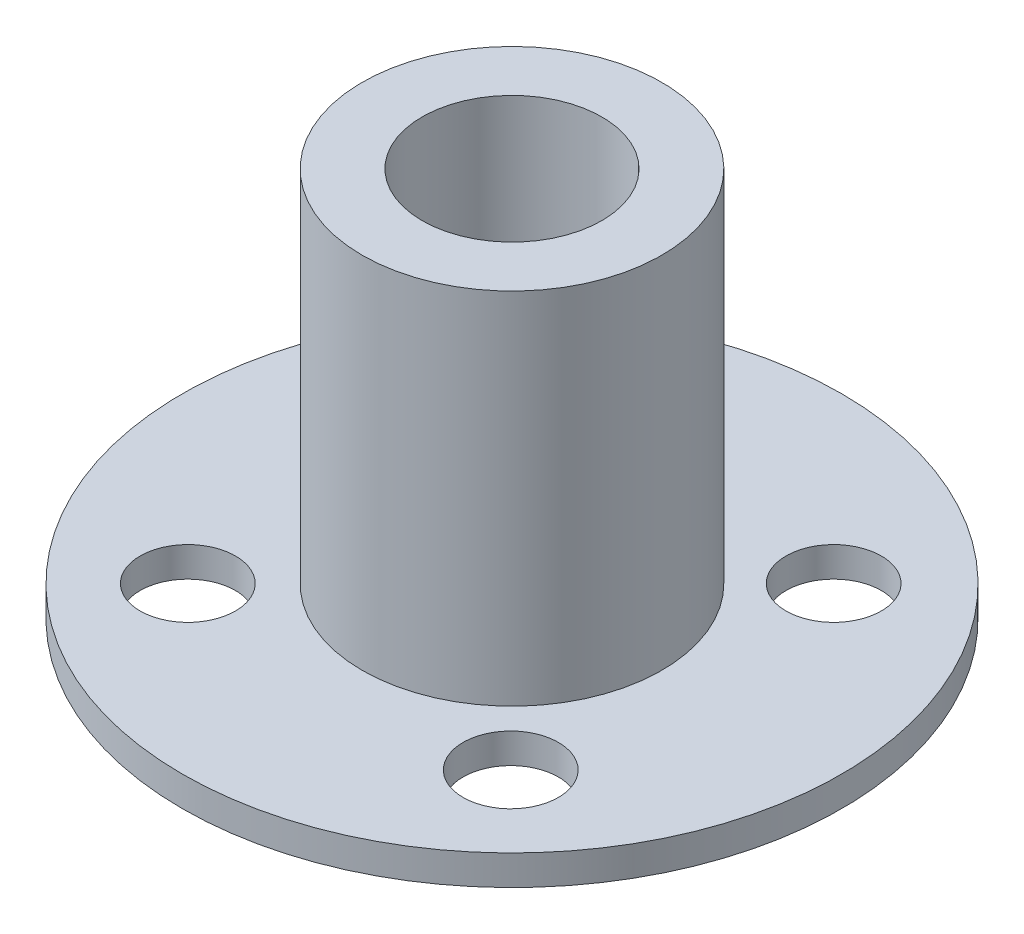
SolidWorks part; units mm, degrees
ref_plane "Front Plane" through (0, 0, 0) normal (0, 0, 1) x (1, 0, 0)
ref_plane "Top Plane" through (0, 0, 0) normal (0, 1, 0) x (1, 0, 0)
ref_plane "Right Plane" through (0, 0, 0) normal (1, 0, 0) x (0, 0, -1)
sketch "Sketch1" plane through (0, 0, 0) normal (0, 1, 0) x (1, 0, 0)
  circle A0 centre (0, 0) radius 11
  dimension "D1" = 22
extrude "Boss-Extrude1" add sketch "Sketch1" along normal blind 1 contours A0
sketch "Sketch2" plane through (0, 1, 0) normal (0, 1, 0) x (1, 0, 0)
  circle A0 centre (0, 0) radius 5
  dimension "D1" = 10
extrude "Boss-Extrude2" add sketch "Sketch2" along normal blind 12
sketch "Sketch3" plane through (0, 13, 0) normal (0, 1, 0) x (1, 0, 0)
  circle A0 centre (0, 0) radius 3
  dimension "D1" = 6
extrude "Cut-Extrude1" cut sketch "Sketch3" against normal blind 12
sketch "Sketch4" plane through (0, 1, 0) normal (0, 1, 0) x (1, 0, 0)
  line L0 (0, 0) -> (0, -11) construction
  line L1 (0, 0) -> (0, 11) construction
  line L2 (-11, 0.03) -> (11, 0.03) construction
  circle A1 centre (0, 0) radius 11 construction
  circle A5 centre (5.3557, 5.381) radius 1.5912
  circle A6 centre (-5.4231, 5.381) radius 1.5912
  circle A7 centre (-5.4231, -5.3978) radius 1.5912
  circle A8 centre (5.3557, -5.3978) radius 1.5912
  point P0 (0, 0)
  point P16 (0, 0)
extrude "Cut-Extrude2" cut sketch "Sketch4" against normal up to next
